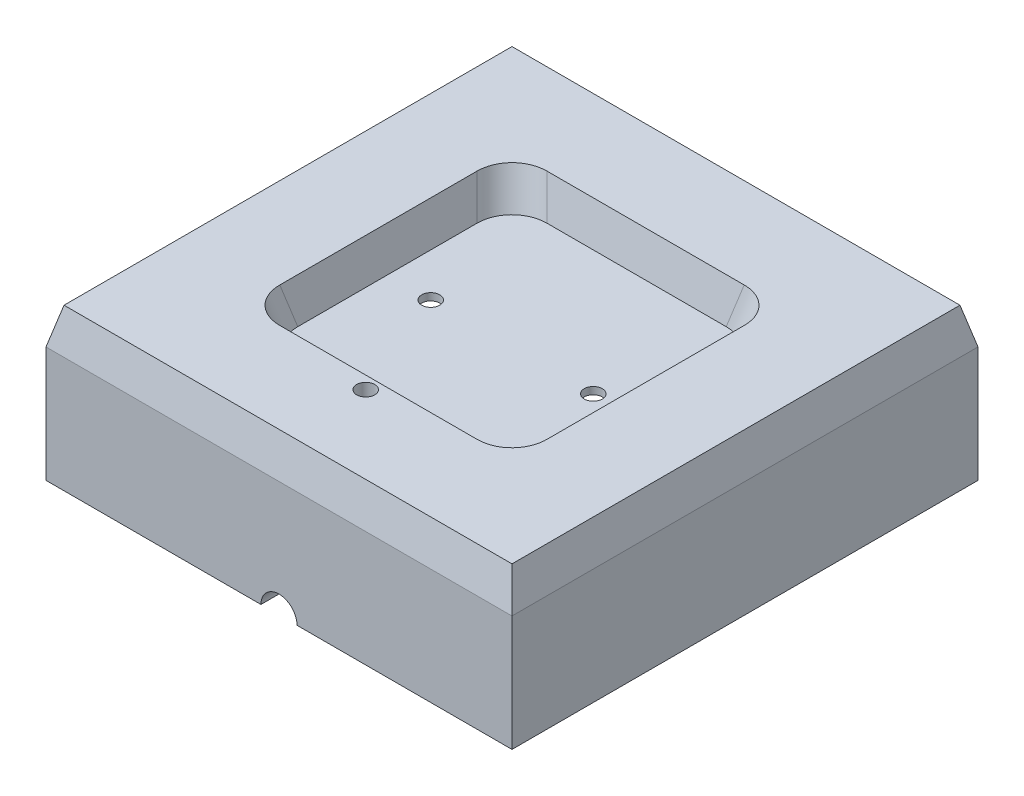
SolidWorks part; units mm, degrees
ref_plane "Front Plane" through (0, 0, 0) normal (0, 0, 1) x (1, 0, 0)
ref_plane "Top Plane" through (0, 0, 0) normal (0, 1, 0) x (1, 0, 0)
ref_plane "Right Plane" through (0, 0, 0) normal (1, 0, 0) x (0, 0, -1)
sketch "Sketch1" plane through (0, 0, 0) normal (0, 1, 0) x (1, 0, 0)
  line L1 (-34.5, -34.5) -> (34.5, -34.5)
  line L2 (-34.5, -34.5) -> (-34.5, 34.5)
  line L3 (-34.5, 34.5) -> (34.5, 34.5)
  line L4 (34.5, -34.5) -> (34.5, 34.5)
  line L5 (-34.5, -34.5) -> (34.5, 34.5) construction
  line L6 (-34.5, 34.5) -> (34.5, -34.5) construction
  point P0 (0, 0)
  dimension "D1" = 69
ref_plane "Plane1" through (0, 10, 0) normal (0, 1, 0) x (1, 0, 0)
extrude "Extrude-Thin1" add sketch "Sketch1" along normal blind 10 draft 14 thin thin type one direction wall 30
fillet "Fillet1" radius 10 4 edges at (35.7466, 5, 35.7466) (35.7466, 5, -35.7466) (-35.7466, 5, -35.7466) (-35.7466, 5, 35.7466)
sketch "Sketch3" plane through (0, 0, 0) normal (0, -1, 0) x (1, 0, 0)
  line L4 (64.5, -64.5) -> (64.5, 64.5)
  line L5 (64.5, 64.5) -> (-64.5, 64.5)
  line L6 (-64.5, 64.5) -> (-64.5, -64.5)
  line L7 (-64.5, -64.5) -> (64.5, -64.5)
  line L8 (64.5, -64.5) -> (64.5, 64.5)
  line L9 (64.5, 64.5) -> (-64.5, 64.5)
  line L10 (-64.5, 64.5) -> (-64.5, -64.5)
  line L11 (-64.5, -64.5) -> (64.5, -64.5)
  dimension "D1" = 0
extrude "Boss-Extrude1" add sketch "Sketch3" along normal blind 2
sketch "Sketch4" plane through (0, 0, 0) normal (0, 1, 0) x (1, 0, 0)
  line L0 (-2.9848, 0) -> (-16.8616, 0) construction
  circle A0 centre (-22.5, 0) radius 2.5
  dimension "D1" = 5
  dimension "D2" = 22.5
extrude "Cut-Extrude1" cut sketch "Sketch4" against normal up to surface (2 mm away) up to face at (0, -2, 0)
ref_plane "Plane2" through (0, 0, 0) normal (1, 0, 0) x (0, 0, -1)
mirror "Mirror1" about plane through (0, 0, 0) normal (1, 0, 0) of "Cut-Extrude1"
sketch "Sketch5" plane through (0, -2, 0) normal (0, -1, 0) x (1, 0, 0)
  line L1 (-64.5, -64.5) -> (64.5, -64.5) construction
  line L2 (64.5, -64.5) -> (64.5, 64.5) construction
  line L3 (64.5, 64.5) -> (-64.5, 64.5) construction
  line L4 (-64.5, 64.5) -> (-64.5, -64.5) construction
  line L5 (-64.5, -64.5) -> (64.5, -64.5)
  line L6 (64.5, -64.5) -> (64.5, 64.5)
  line L7 (64.5, 64.5) -> (-64.5, 64.5)
  line L8 (-64.5, 64.5) -> (-64.5, -64.5)
extrude "Extrude-Thin2" add sketch "Sketch5" along normal blind 30 thin thin type one direction reverse wall 5
sketch "Sketch6" plane through (0, 0, 64.5) normal (0, 0, 1) x (1, 0, 0)
  line L0 (64.5, -32) -> (-64.5, -32) construction
  line L1 (-5, -32) -> (5, -32)
  arc A0 (-5, -32) -> (5, -32) centre (0, -32) cw
  dimension "D1" = 5
extrude "Cut-Extrude2" cut sketch "Sketch6" against normal up to surface (5 mm away) up to face at (0, -17, 59.5)
sketch "Sketch7" plane through (0, 10, 0) normal (0, 1, 0) x (1, 0, 0)
  line L0 (0, -23.1) -> (0, 23.1) construction
  line L2 (-27.2903, -36.9933) -> (27.2903, -36.9933) construction
  circle A0 centre (0, -40.4933) radius 2.5
  point P4 (0, 0)
  dimension "D1" = 5
  dimension "D2" = 3.5
extrude "Cut-Extrude3" cut sketch "Sketch7" against normal up to surface (12 mm away) up to face at (0, -2, 0)
